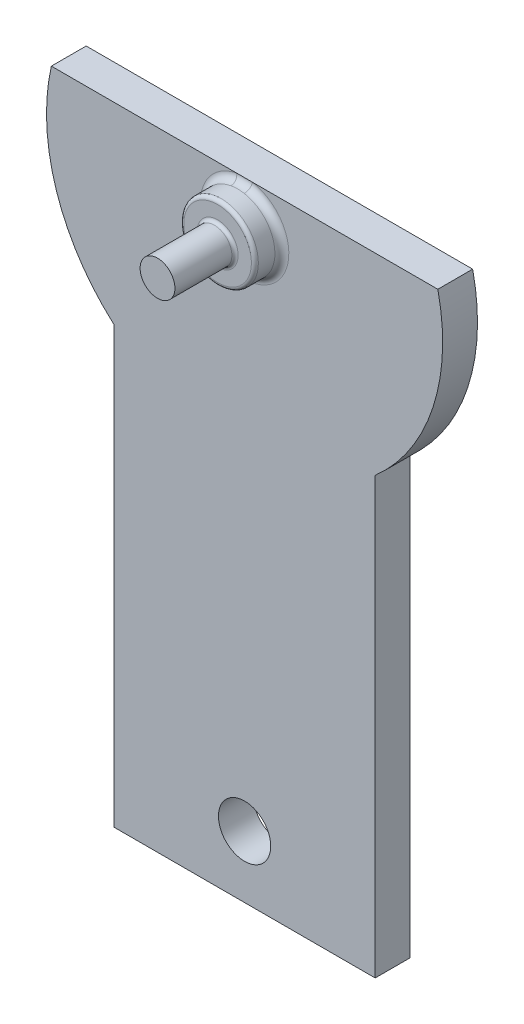
SolidWorks part; units mm, degrees
ref_plane "Front Plane" through (0, 0, 0) normal (0, 0, 1) x (1, 0, 0)
ref_plane "Top Plane" through (0, 0, 0) normal (0, 1, 0) x (1, 0, 0)
ref_plane "Right Plane" through (0, 0, 0) normal (1, 0, 0) x (0, 0, -1)
sketch "Sketch1" plane through (0, 0, 0) normal (0, 0, 1) x (1, 0, 0)
  line L0 (0, 150.6274) -> (0, -208.1955) construction
  line L1 (75, -335.5223) -> (75, -85.5223)
  line L2 (75, -335.5223) -> (-75, -335.5223)
  line L3 (-75, -335.5223) -> (-75, -85.5223)
  line L4 (-110.9687, 25) -> (110.9687, 25)
  arc A0 (-110.9687, 25) -> (110.9687, 25) centre (0, 0) ccw
  circle A1 centre (0, 0) radius 10
  point P10 (0, -335.5223)
  dimension "D1" = 227.5
  dimension "D2" = 20
  dimension "D3" = 25
  dimension "D4" = 250
  dimension "D5" = 150
extrude "Boss-Extrude1" add sketch "Sketch1" along normal blind 20 contours A0 L3 L2 L1 | L0 L4 A0 A1 | L4 L0 A1 A0 | L0 A1 | A1 L0 region at (50.6064, -35.5134, 0) region at (-50.6064, -35.5134, 0) region at (4.2441, 0, 0) region at (-4.2441, 0, 0) region at (0, -220.0462, 0)
extrude "Boss-Extrude2" add sketch "Sketch1<3>" along normal up to surface (50 mm away) from surface contours A1 starting at face at (0, -133.6618, 20)
sketch "Sketch1<3>" plane through (0, 0, 0) normal (0, 0, 1) x (1, 0, 0) same geometry as "Sketch1"
sketch "Sketch2" plane through (0, 0, 20) normal (0, 0, 1) x (1, 0, 0)
  circle A0 centre (0, -300) radius 15
  dimension "D2" = 30
  dimension "D1" = 300
extrude "Cut-Extrude1" cut sketch "Sketch2" against normal up to surface (20 mm away) contours A0 up to face at (0, -133.6618, 0)
sketch "Sketch3" plane through (0, 0, 20) normal (0, 0, 1) x (1, 0, 0)
  circle A2 centre (0, 0) radius 21.4099
extrude "Boss-Extrude3" add sketch "Sketch3" along normal blind 15.5
fillet "Fillet1" radius 1.8 1 edges at (10, 0, 35.5)
fillet "Fillet2" radius 4 1 edges at (21.4099, 0, 20)
fillet "Fillet3" radius 2 1 edges at (21.4099, 0, 35.5)
